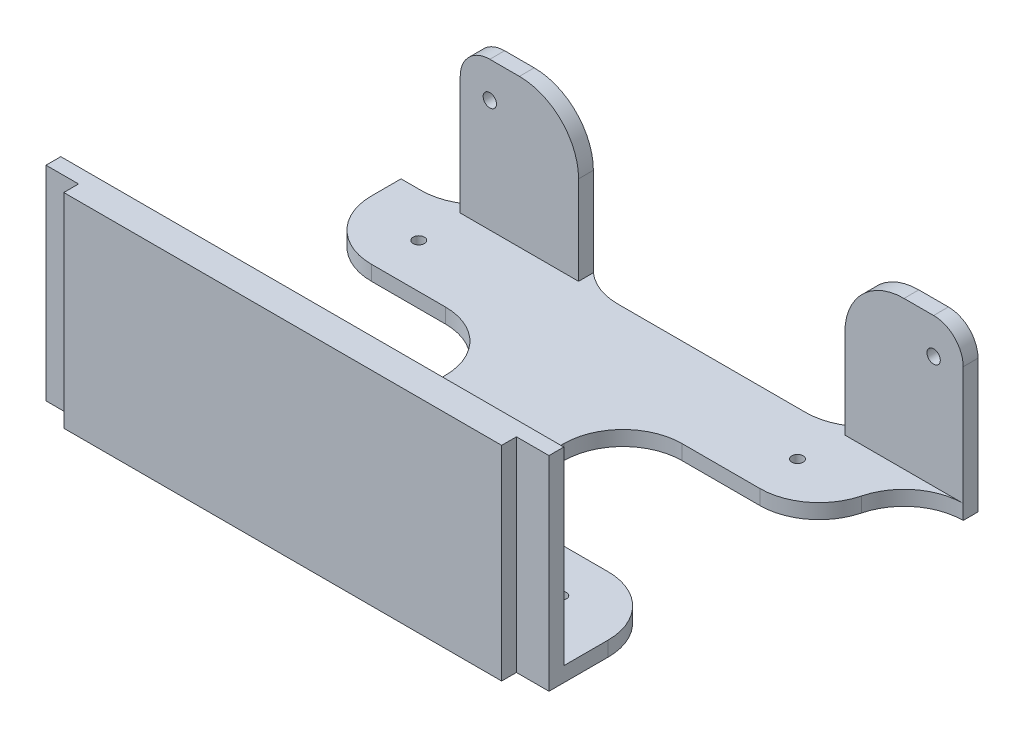
SolidWorks part; units mm, degrees
ref_plane "Front Plane" through (0, 0, 0) normal (0, 0, 1) x (1, 0, 0)
ref_plane "Top Plane" through (0, 0, 0) normal (0, 1, 0) x (1, 0, 0)
ref_plane "Right Plane" through (0, 0, 0) normal (1, 0, 0) x (0, 0, -1)
sketch "Sketch1" plane through (0, 0, 0) normal (0, 1, 0) x (1, 0, 0)
  line L0 (-85, -57.5) -> (85, -57.5)
  line L1 (85, 62.5) -> (-85, 62.5)
  line L2 (85, 62.5) -> (85, -62.5)
  line L3 (85, -62.5) -> (-85, -62.5)
  line L4 (-85, 62.5) -> (-85, -62.5)
  line L5 (85, 62.5) -> (-85, -62.5) construction
  line L6 (85, -62.5) -> (-85, 62.5) construction
  line L7 (-74, -62.5) -> (74, -62.5)
  line L8 (-74, -62.5) -> (-74, -67.5)
  line L9 (-74, -67.5) -> (74, -67.5)
  line L10 (74, -62.5) -> (74, -67.5)
  line L11 (-85, 57.5) -> (85, 57.5)
  line L16 (-65, 62.5) -> (-65, 57.5)
  line L17 (85, 57.5) -> (105, 57.5)
  line L18 (85, 57.5) -> (85, 62.5)
  line L19 (85, 62.5) -> (105, 62.5)
  line L20 (105, 57.5) -> (105, 62.5)
  line L22 (-85, 27.5) -> (-20, 27.5)
  line L23 (-85, 27.5) -> (-85, -22.5)
  line L24 (-85, -22.5) -> (-20, -22.5)
  line L25 (-20, 27.5) -> (-20, -22.5)
  line L26 (85, 27.5) -> (20, 27.5)
  line L27 (85, 27.5) -> (85, -22.5)
  line L28 (85, -22.5) -> (20, -22.5)
  line L29 (20, 27.5) -> (20, -22.5)
  circle A0 centre (-64, -37.5) radius 1.9
  circle A1 centre (64, -37.5) radius 1.9
  circle A2 centre (-64, 42.5) radius 1.9
  circle A3 centre (64, 42.5) radius 1.9
  point P0 (0, 0)
  point P26 (0, 0)
  dimension "D10" = 30
  dimension "D11" = 10
  dimension "D12" = 10
  dimension "D13" = 30
  dimension "D14" = 3.8
  dimension "D15" = 80
  dimension "D1" = 170
  dimension "D2" = 148
  dimension "D3" = 11
  dimension "D4" = 5
  dimension "D5" = 5
  dimension "D6" = 5
  dimension "D7" = 115
  dimension "D8" = 20
  dimension "D9" = 20
  dimension "D16" = 35
  dimension "D17" = 30
  dimension "D18" = 40
extrude "Boss-Extrude1" add sketch "Sketch1" along normal blind 5 contours L11 L4 L0 L2 region at (0, 0, 1.2583)
extrude "Boss-Extrude3" add sketch "Sketch1<4>" along normal blind 69 contours L10 L3 L8 L9 | L0 L4 L3 L2 region at (0, 0, 60) region at (0, 0, 65)
sketch "Sketch1<4>" plane through (0, 0, 0) normal (0, 1, 0) x (1, 0, 0) same geometry as "Sketch1"
extrude "Boss-Extrude4" add sketch "Sketch1<5>" along normal blind 55 contours L1 L16 L11 L2 | L17 L20 L19 L2 region at (10, 0, -60) region at (95, 0, -60)
sketch "Sketch1<5>" plane through (0, 0, 0) normal (0, 1, 0) x (1, 0, 0) same geometry as "Sketch1"
sketch "Sketch2" plane through (0, 0, -62.5) normal (0, 0, -1) x (-1, 0, 0)
  line L4 (-105, 55) -> (-105, 0) construction
  line L5 (-105, 0) -> (65, 0) construction
  circle A0 centre (-95, 43) radius 2.25
  circle A1 centre (55, 43) radius 2.25
  point P8 (0, 0)
  point P9 (0, 0)
  point P10 (0, 0)
  dimension "D1" = 10
  dimension "D2" = 43
  dimension "D3" = 4.5
  dimension "D4" = 150
extrude "Cut-Extrude1" cut sketch "Sketch2" against normal blind 60
fillet "Fillet1" radius 20 1 edges at (85, 2.5, -57.5)
fillet "Fillet2" radius 10 2 edges at (-65, 55, -60) (105, 55, -60)
sketch "Sketch4" plane through (0, 55, 0) normal (0, 1, 0) x (1, 0, 0)
  line L0 (95, 62.5) -> (-55, 62.5) construction
  line L1 (-25, 62.5) -> (65, 62.5)
  line L2 (-25, 62.5) -> (-25, 57.5)
  line L3 (-25, 57.5) -> (65, 57.5)
  line L4 (65, 62.5) -> (65, 57.5)
  line L5 (-55, 57.5) -> (95, 57.5) construction
  line L6 (-65, 57.5) -> (-65, 62.5) construction
  line L7 (105, 62.5) -> (105, 57.5) construction
  dimension "D1" = 40
  dimension "D2" = 40
extrude "Cut-Extrude2" cut sketch "Sketch4" against normal blind 55
fillet "Fillet3" radius 20 13 edges at (-25, 55, -60) (65, 55, -60) (65, 2.5, -57.5) (-25, 2.5, -57.5) (-20, 2.5, 22.5) (-20, 2.5, -27.5) (85, 2.5, -27.5) (-85, 2.5, -27.5) (-85, 2.5, 22.5) (85, 2.5, 22.5) (20, 2.5, 22.5) (20, 2.5, -27.5) (-65, 2.5, -57.5)
